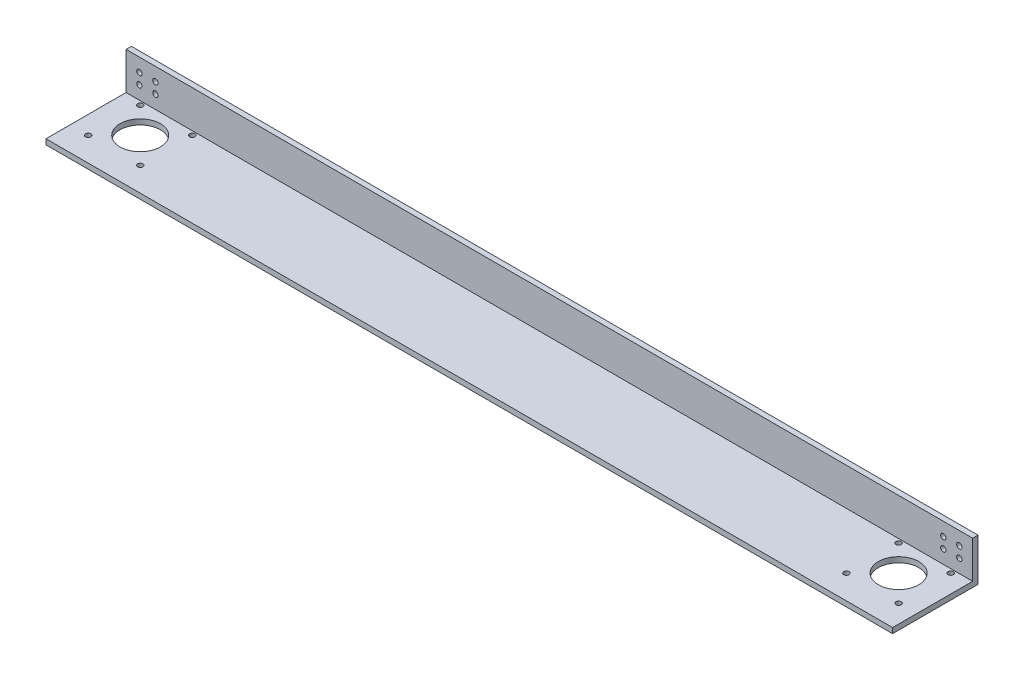
SolidWorks part; units mm, degrees
ref_plane "Front Plane" through (0, 0, 0) normal (0, 0, 1) x (1, 0, 0)
ref_plane "Top Plane" through (0, 0, 0) normal (0, 1, 0) x (1, 0, 0)
ref_plane "Right Plane" through (0, 0, 0) normal (1, 0, 0) x (0, 0, -1)
sketch "Sketch1" plane through (0, 0, 0) normal (1, 0, 0) x (0, 0, -1)
  line L0 (0, 0) -> (-50.8, 0)
  line L1 (-50.8, 0) -> (-50.8, 3.175)
  line L2 (-50.8, 3.175) -> (-3.175, 3.175)
  line L3 (-3.175, 3.175) -> (-3.175, 25.4)
  line L4 (-3.175, 25.4) -> (0, 25.4)
  line L5 (0, 25.4) -> (0, 0)
  dimension "LHeight" = 25.4
  dimension "LWidth" = 50.8
  dimension "LMaterialThickness" = 3.175
  dimension "D1" = 47.625
  dimension "D2" = 22.225
  dimension "D3" = 3.175
extrude "Boss-Extrude1" add sketch "Sketch1" along normal blind 503.65
sketch "TopHoles-Sketch2" plane through (0, 3.175, 0) normal (0, 1, 0) x (1, 0, 0)
  line L2 (0, -3.175) -> (0, -50.8) construction
  line L3 (503.65, -3.175) -> (503.65, -50.8) construction
  circle A0 centre (26.25, -21) radius 12
  circle A1 centre (477.4, -21) radius 12
  circle A2 centre (10.75, -5.5) radius 1.5875
  circle A3 centre (41.75, -5.5) radius 1.5875
  circle A4 centre (461.9, -5.5) radius 1.5875
  circle A5 centre (492.9, -5.5) radius 1.5875
  circle A6 centre (10.75, -36.5) radius 1.5875
  circle A7 centre (41.75, -36.5) radius 1.5875
  circle A8 centre (461.9, -36.5) radius 1.5875
  circle A9 centre (492.9, -36.5) radius 1.5875
  dimension "D9" = 3.175
  dimension "D10" = 24
  dimension "D2" = 5.5
  dimension "D3" = 31
  dimension "D4" = 15.5
  dimension "D5" = 15.5
  dimension "D6" = 31
  dimension "D7" = 15.5
  dimension "D13" = 26.25
  dimension "D8" = 31
  dimension "D11" = 26.25
extrude "TopHoles-Cut-Extrude1" cut sketch "TopHoles-Sketch2" against normal through all
sketch "BackSideHoles-Sketch3" plane through (0, 0, 0) normal (0, 0, -1) x (-1, 0, 0)
  line L1 (-503.65, 25.4) -> (0, 25.4) construction
  line L2 (0, 0) -> (0, 25.4) construction
  line L3 (-503.65, 0) -> (-503.65, 25.4) construction
  circle A0 centre (-495.7125, 17.4625) radius 1.5875
  circle A1 centre (-486.1875, 17.4625) radius 1.5875
  circle A2 centre (-495.7125, 11.1125) radius 1.5875
  circle A3 centre (-486.1875, 11.1125) radius 1.5875
  circle A4 centre (-7.9375, 11.1125) radius 1.5875
  circle A5 centre (-17.4625, 11.1125) radius 1.5875
  circle A6 centre (-17.4625, 17.4625) radius 1.5875
  circle A7 centre (-7.9375, 17.4625) radius 1.5875
  dimension "D7" = 3.175
  dimension "D4" = 11.1125
  dimension "D3" = 7.9375
  dimension "D1" = 7.9375
  dimension "D2" = 17.4625
  dimension "D6" = 17.4625
  dimension "D5" = 7.9375
extrude "BackSideHoles-Cut-Extrude2" cut sketch "BackSideHoles-Sketch3" against normal through all
equation "\"MidBackRailWidth\"= 2.00in"
equation "\"MidBackRailHeight\"= 1.00in"
equation "\"RailThickness\"= .125in'Spec"
equation "\"SideRailHoleY1FromEdge\"= \"HoleOffsetFromEdge\""
equation "\"SideRailHoleX1FromSide\"= \"HoleOffsetFromSide\""
equation "\"StepperHoleDiameter\"= 24mm"
equation "\"StepperMountingHoleDiameter\"= 3.175mm"
equation "\"StepperMountingHoleDistance\"= 31mm'Spec"
equation "\"VSWidth\"= 1.25in'Spec"
equation "\"StepperMountingHoleOffsetFromLeftRightEdge\"= \"StepperMountingHoleOffsetFromItsSide\""
equation "\"HoleOffsetFromEdge\"= \"RailThickness\" * 2.5"
equation "\"HoleOffsetFromSide\"= \"RailThickness\" * 3.5"
equation "\"StepperMountingHoleOffsetFromItsSide\"= 5.5mm'Spec"
equation "\"SideRailHoleX2FromSide\"= \"VSWidth\" - \"HoleOffsetFromEdge\" - \"RailThickness\"'Equals 20.6375"
equation "\"FasteningHoleDiameter\"= .125in"
equation "\"SideRailHoleY2FromSide\"= \"HoleOffsetFromSide\""
equation "\"FrontBackRailLength\"= 510mm"
equation "\"LHeight@Sketch1\"=\"MidBackRailHeight\""
equation "\"LWidth@Sketch1\"=\"MidBackRailWidth\""
equation "\"D2@TopHoles-Sketch2\" = \"StepperMountingHoleOffsetFromLeftRightEdge\""
equation "\"D3@TopHoles-Sketch2\" = \"StepperMountingHoleDistance\""
equation "\"D4@TopHoles-Sketch2\" = \"StepperMountingHoleDistance\" / 2"
equation "\"D5@TopHoles-Sketch2\" = \"StepperMountingHoleDistance\" / 2"
equation "\"D6@TopHoles-Sketch2\" = \"StepperMountingHoleDistance\""
equation "\"D7@TopHoles-Sketch2\" = \"StepperMountingHoleDistance\" / 2"
equation "\"D9@TopHoles-Sketch2\" = \"StepperMountingHoleDiameter\""
equation "\"D10@TopHoles-Sketch2\" = \"StepperHoleDiameter\""
equation "\"D4@BackSideHoles-Sketch3\" = \"SideRailHoleY2FromSide\""
equation "\"D7@BackSideHoles-Sketch3\" = \"FasteningHoleDiameter\""
equation "\"D1@Boss-Extrude1\"= \"MidBackRailLength\""
equation "\"D3@BackSideHoles-Sketch3\"=\"SideRailHoleY1FromEdge\""
equation "\"D1@BackSideHoles-Sketch3\"=\"SideRailHoleX1FromSide\" - \"RailThickness\""
equation "\"D2@BackSideHoles-Sketch3\"=\"SideRailHoleX2FromSide\" - \"RailThickness\""
equation "\"D6@BackSideHoles-Sketch3\"=\"SideRailHoleX2FromSide\" - \"RailThickness\""
equation "\"D5@BackSideHoles-Sketch3\"=\"SideRailHoleX1FromSide\" - \"RailThickness\""
equation "\"StepperHoleToAlignHorizontallyWithGantryBlock\"= \"LinearGBWithRailDepth\" + \"GABDistanceFromBackToFirstPulley\"'Equals 26.25"
equation "\"D13@TopHoles-Sketch2\"=\"StepperHoleToAlignHorizontallyWithGantryBlock\" "
equation "\"D8@TopHoles-Sketch2\"=\"StepperMountingHoleDistance\""
equation "\"D11@TopHoles-Sketch2\"=\"StepperHoleToAlignHorizontallyWithGantryBlock\" "
equation "\"LinearGBWithRailDepth\"= 12.75mm'Spec"
equation "\"GABDistanceFromBackToFirstPulley\"= 13.5mm"
equation "\"MidBackRailLength\"= \"FrontBackRailLength\" - \"RailThickness\" * 2'MidBackRail buts up against MidSideRail"
